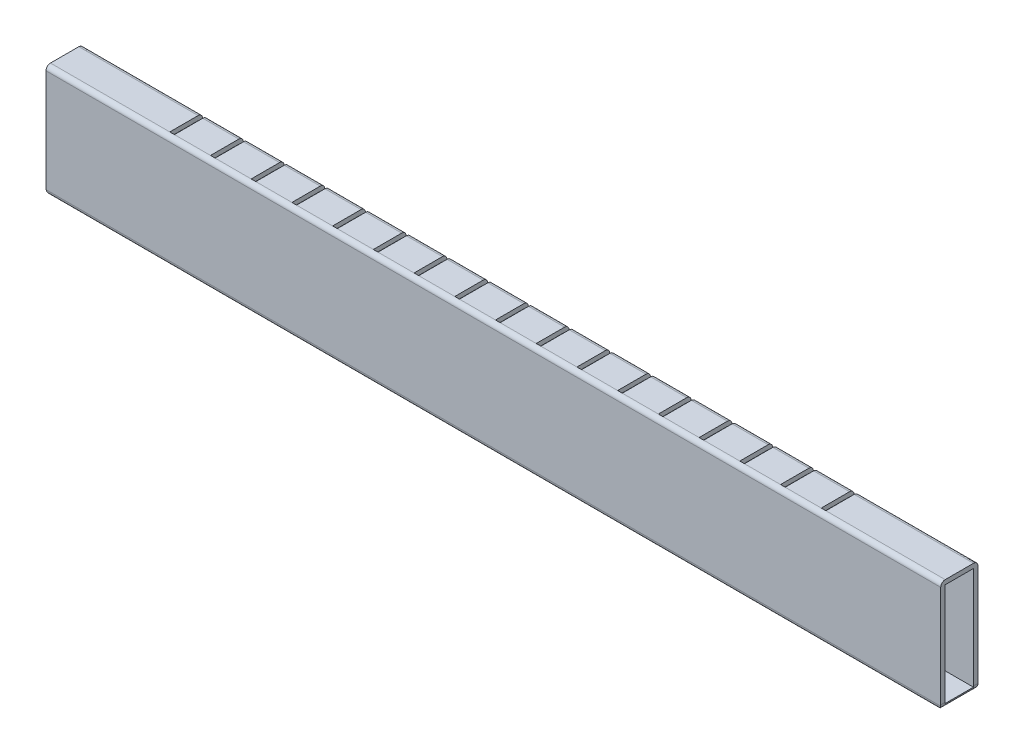
SolidWorks part; units mm, degrees
ref_plane "Front Plane" through (0, 0, 0) normal (0, 0, 1) x (1, 0, 0)
ref_plane "Top Plane" through (0, 0, 0) normal (0, 1, 0) x (1, 0, 0)
ref_plane "Right Plane" through (0, 0, 0) normal (1, 0, 0) x (0, 0, -1)
sketch "Sketch1" plane through (0, 0, 0) normal (1, 0, 0) x (0, 0, -1)
  line L0 (3.048, 3.048) -> (3.048, 73.152)
  line L1 (3.048, 0) -> (22.352, 0)
  line L2 (0, 3.048) -> (0, 73.152)
  line L3 (3.048, 76.2) -> (22.352, 76.2)
  line L4 (25.4, 3.048) -> (25.4, 73.152)
  line L5 (3.048, 73.152) -> (22.352, 73.152)
  line L6 (22.352, 3.048) -> (22.352, 73.152)
  line L7 (3.048, 3.048) -> (22.352, 3.048)
  arc A0 (3.048, 0) -> (0, 3.048) centre (3.048, 3.048) cw
  arc A1 (22.352, 0) -> (25.4, 3.048) centre (22.352, 3.048) ccw
  arc A2 (22.352, 76.2) -> (25.4, 73.152) centre (22.352, 73.152) cw
  arc A3 (0, 73.152) -> (3.048, 76.2) centre (3.048, 73.152) cw
  arc A4 (3.048, 73.152) -> (3.048, 73.152) centre (3.048, 73.152) cw
  arc A5 (22.352, 73.152) -> (22.352, 73.152) centre (22.352, 73.152) cw
  arc A6 (22.352, 3.048) -> (22.352, 3.048) centre (22.352, 3.048) ccw
  arc A7 (3.048, 3.048) -> (3.048, 3.048) centre (3.048, 3.048) cw
  point P7 (0, 0)
  point P10 (25.4, 0)
  point P13 (25.4, 76.2)
  dimension "D3" = 3.048
  dimension "D1" = 25.4
  dimension "D2" = 76.2
  dimension "D4" = 3.048
extrude "Boss-Extrude1" add sketch "Sketch1" along normal blind 609.6
sketch "Sketch2" plane through (0, 76.2, 0) normal (0, 1, 0) x (1, 0, 0)
  line L0 (609.6, 3.048) -> (0, 3.048) construction
  line L1 (609.6, 3.048) -> (0, 3.048) construction
  line L2 (0, 22.352) -> (0, 3.048) construction
  line L3 (81.28, 3.048) -> (84.455, 3.048)
  line L4 (81.28, 3.048) -> (81.28, 41.148)
  line L5 (81.28, 41.148) -> (84.455, 41.148)
  line L6 (84.455, 3.048) -> (84.455, 41.148)
  dimension "D1" = 3.175
  dimension "D2" = 81.28
  dimension "D3" = 38.1
extrude "Cut-Extrude1" cut sketch "Sketch2" against normal blind 38.1
pattern_linear "LPattern1" count 17 spacing 27.7419 along (1, 0, 0) of "Cut-Extrude1"
fillet "Fillet1" radius 3.81 2 edges at (609.6, 0, -12.7) (0, 0, -12.7)
sketch "Sketch4" plane through (0, 0, -25.4) normal (0, 0, -1) x (-1, 0, 0)
  line L9 (-535.7788, 55.7232) -> (-535.7788, 80.7232) construction
  line L10 (-541.0288, 80.7232) -> (-541.0288, 55.7232) construction
  line L11 (-575.7788, 55.7232) -> (-575.7788, 80.7232) construction
  line L12 (-581.0288, 80.7232) -> (-581.0288, 55.7232) construction
  line L13 (-573.7788, 18.3482) -> (-579.0288, 18.3482) construction
  line L14 (-579.0288, 13.0982) -> (-573.7788, 13.0982) construction
  line L15 (-537.5288, 18.3482) -> (-542.7788, 18.3482) construction
  line L16 (-542.7788, 13.0982) -> (-537.5288, 13.0982) construction
  line L17 (-535.7788, 55.7232) -> (-535.7788, 80.7232) construction
  line L18 (-541.0288, 80.7232) -> (-541.0288, 55.7232) construction
  line L19 (-575.7788, 55.7232) -> (-575.7788, 80.7232) construction
  line L20 (-581.0288, 80.7232) -> (-581.0288, 55.7232) construction
  line L21 (-573.7788, 18.3482) -> (-579.0288, 18.3482) construction
  line L22 (-579.0288, 13.0982) -> (-573.7788, 13.0982) construction
  line L23 (-537.5288, 18.3482) -> (-542.7788, 18.3482) construction
  line L24 (-542.7788, 13.0982) -> (-537.5288, 13.0982) construction
  arc A11 (-535.7788, 80.7232) -> (-541.0288, 80.7232) centre (-538.4038, 80.7232) ccw construction
  arc A12 (-575.7788, 80.7232) -> (-581.0288, 80.7232) centre (-578.4038, 80.7232) ccw construction
  arc A13 (-581.0288, 55.7232) -> (-575.7788, 55.7232) centre (-578.4038, 55.7232) ccw construction
  arc A14 (-573.7788, 13.0982) -> (-573.7788, 18.3482) centre (-573.7788, 15.7232) ccw construction
  arc A15 (-579.0288, 18.3482) -> (-579.0288, 13.0982) centre (-579.0288, 15.7232) ccw construction
  arc A16 (-537.5288, 13.0982) -> (-537.5288, 18.3482) centre (-537.5288, 15.7232) ccw construction
  arc A17 (-542.7788, 18.3482) -> (-542.7788, 13.0982) centre (-542.7788, 15.7232) ccw construction
  arc A18 (-541.0288, 55.7232) -> (-535.7788, 55.7232) centre (-538.4038, 55.7232) ccw construction
  arc A19 (-535.7788, 80.7232) -> (-541.0288, 80.7232) centre (-538.4038, 80.7232) ccw construction
  arc A20 (-575.7788, 80.7232) -> (-581.0288, 80.7232) centre (-578.4038, 80.7232) ccw construction
  arc A21 (-581.0288, 55.7232) -> (-575.7788, 55.7232) centre (-578.4038, 55.7232) ccw construction
  arc A22 (-573.7788, 13.0982) -> (-573.7788, 18.3482) centre (-573.7788, 15.7232) ccw construction
  arc A23 (-579.0288, 18.3482) -> (-579.0288, 13.0982) centre (-579.0288, 15.7232) ccw construction
  arc A24 (-537.5288, 13.0982) -> (-537.5288, 18.3482) centre (-537.5288, 15.7232) ccw construction
  arc A25 (-542.7788, 18.3482) -> (-542.7788, 13.0982) centre (-542.7788, 15.7232) ccw construction
  arc A26 (-541.0288, 55.7232) -> (-535.7788, 55.7232) centre (-538.4038, 55.7232) ccw construction
  circle A27 centre (-578.4038, 62.0732) radius 2.625
  circle A28 centre (-538.4038, 62.0732) radius 2.625
  circle A29 centre (-540.0688, 15.7232) radius 2.625
  circle A30 centre (-576.3188, 15.7232) radius 2.625
  dimension "D2" = 5.25
  dimension "D3" = 5.25
  dimension "D5" = 5.25
  dimension "D8" = 5.25
  dimension "D1" = 6.35
  dimension "D4" = 6.35
  dimension "D6" = 2.54
  dimension "D7" = 2.54
extrude "Cut-Extrude2" cut sketch "Sketch4" against normal blind 6.35
pattern_linear "LPattern2" count 2 spacing 507.1999 along (-1, 0, 0) of "Cut-Extrude2"
